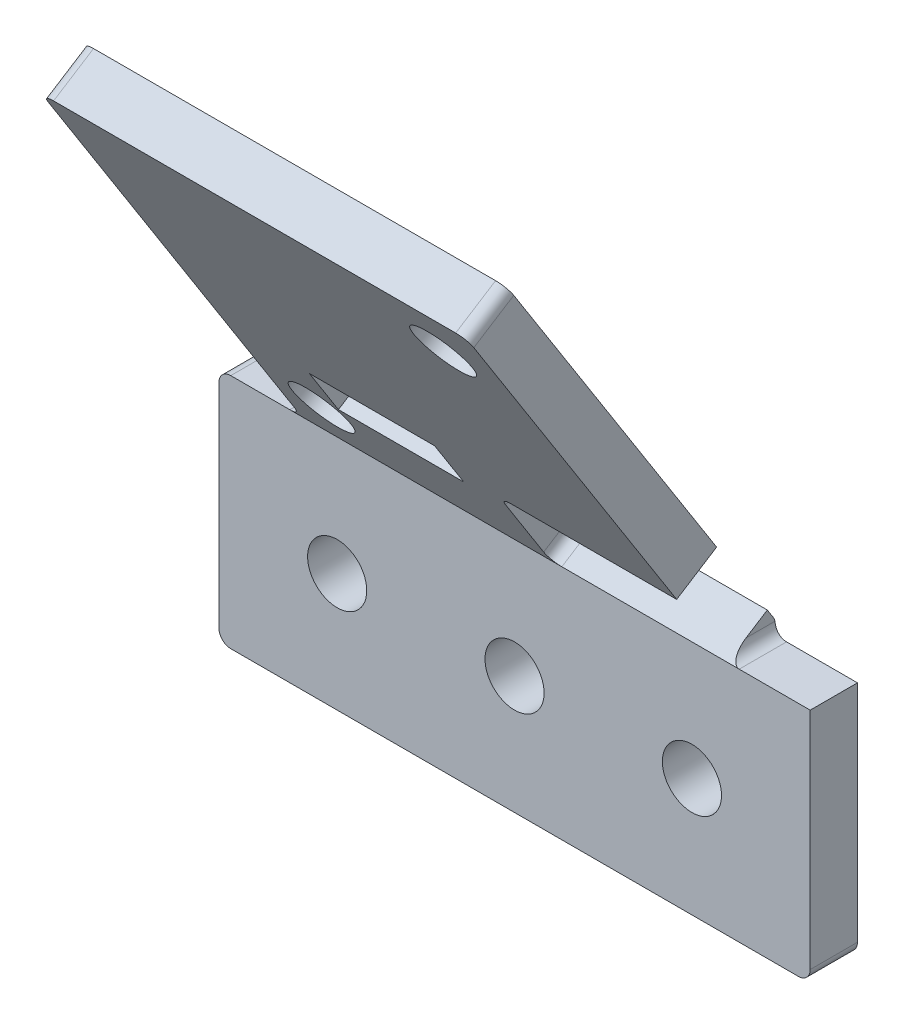
SolidWorks part; units mm, degrees
ref_plane "前视基准面" through (0, 0, 0) normal (0, 0, 1) x (1, 0, 0)
ref_plane "上视基准面" through (0, 0, 0) normal (0, 1, 0) x (1, 0, 0)
ref_plane "右视基准面" through (0, 0, 0) normal (1, 0, 0) x (0, 0, -1)
sketch "草图1" plane through (0, 0, 0) normal (0, 0, 1) x (1, 0, 0)
  line L1 (25, -10) -> (-25, -10)
  line L2 (25, -10) -> (25, 10)
  line L3 (25, 10) -> (-25, 10)
  line L4 (-25, -10) -> (-25, 10)
  line L5 (25, -10) -> (-25, 10) construction
  line L6 (25, 10) -> (-25, -10) construction
  point P0 (0, 0)
  dimension "D1" = 20
  dimension "D2" = 50
extrude "凸台-拉伸1" add sketch "草图1" along normal blind 4
sketch "草图4" plane through (0, 0, 0) normal (1, 0, 0) x (0, 0, -1)
  line L0 (-4, 10) -> (-25.9804, 44.6101)
  line L1 (-25.9804, 44.6101) -> (-22.6038, 46.7546)
  line L2 (-22.6038, 46.7546) -> (0.0489, 11.0858)
  line L3 (0.0489, 11.0858) -> (0, 10)
  line L4 (-4, 10) -> (0, 10)
  dimension "D1" = 145
  dimension "D2" = 41
  dimension "D3" = 4
extrude "凸台-拉伸2" add sketch "草图4" along normal mid plane 36
sketch "草图5" plane through (0, 1.0639, -1.6752) normal (0, -0.5361, 0.8441) x (1, 0, 0)
  line L0 (18, 51.5859) -> (-18, 10.5859) construction
  circle A2 centre (12.7216, 45.5744) radius 1.5
  circle A3 centre (-13.6705, 15.5168) radius 1.5
  dimension "D1" = 8
  dimension "D2" = 3
  dimension "D3" = 3
  dimension "D4" = 40
extrude "切除-拉伸1" cut sketch "草图5" against normal through all contours A2 | A2 | A3 | A3 region at (12.7216, 39.5355, 22.7576) region at (-13.6705, 14.1624, 6.6435)
sketch "草图6" plane through (0, 1.0639, -1.6752) normal (0, -0.5361, 0.8441) x (1, 0, 0)
  line L1 (18, 10.5859) -> (3, 10.5859)
  line L2 (18, 10.5859) -> (18, 18.5859)
  line L3 (18, 18.5859) -> (3, 18.5859)
  line L4 (3, 10.5859) -> (3, 18.5859)
  dimension "D1" = 15
  dimension "D2" = 8
extrude "切除-拉伸2" cut sketch "草图6" against normal through all
fillet "圆角1" radius 1 2 edges at (3, 11.0722, 2.3117) (3, 17.8254, 6.6006)
fillet "圆角2" radius 1 7 edges at (25, -10, 2) (-25, -10, 2) (-18, 45.6824, 24.2921) (18, 45.6824, 24.2921) (-25, 10, 2) (-18, 10, 2) (18, 10, 2)
fillet "圆角3" radius 1 1 edges at (0, 11.0858, -0.0489)
sketch "草图7" plane through (0, 1.0639, -1.6752) normal (0, -0.5361, 0.8441) x (1, 0, 0)
  circle A0 centre (12.7216, 45.5744) radius 2.5
  circle A1 centre (-13.6705, 15.5168) radius 2.5
  dimension "D1" = 5
  dimension "D2" = 5
extrude "切除-拉伸3" cut sketch "草图7" against normal blind 2
sketch "草图8" plane through (0, 0, 4) normal (0, 0, 1) x (1, 0, 0)
  line L0 (0, -10) -> (0, 0) construction
  line L1 (-24, -10) -> (24, -10) construction
  circle A0 centre (0, 0) radius 2.5
  circle A1 centre (15, 0) radius 2.5
  circle A2 centre (-15, 0) radius 2.5
  dimension "D1" = 5
  dimension "D2" = 10
  dimension "D3" = 2
  dimension "D4" = 2
extrude "切除-拉伸4" cut sketch "草图8" against normal through all
sketch "草图9" plane through (0, 1.0639, -1.6752) normal (0, -0.5361, 0.8441) x (1, 0, 0)
  line L1 (-11, 21.5859) -> (-1, 21.5859)
  line L2 (-11, 21.5859) -> (-11, 17.5859)
  line L3 (-11, 17.5859) -> (-1, 17.5859)
  line L4 (-1, 21.5859) -> (-1, 17.5859)
  line L5 (-0.7, 17.2859) -> (-11.3, 17.2859)
  line L6 (-0.7, 17.2859) -> (-0.7, 21.8859)
  line L7 (-0.7, 21.8859) -> (-11.3, 21.8859)
  line L8 (-11.3, 17.2859) -> (-11.3, 21.8859)
  line L9 (-0.7, 17.2859) -> (-11.3, 21.8859) construction
  line L10 (-0.7, 21.8859) -> (-11.3, 17.2859) construction
  point P6 (-6, 19.5859)
  dimension "D1" = 0.3
  dimension "D2" = 0.3
  dimension "D3" = 0.3
  dimension "D4" = 0.3
extrude "切除-拉伸5" cut sketch "草图9" against normal blind 10 contours L7 L8 L5 L6
